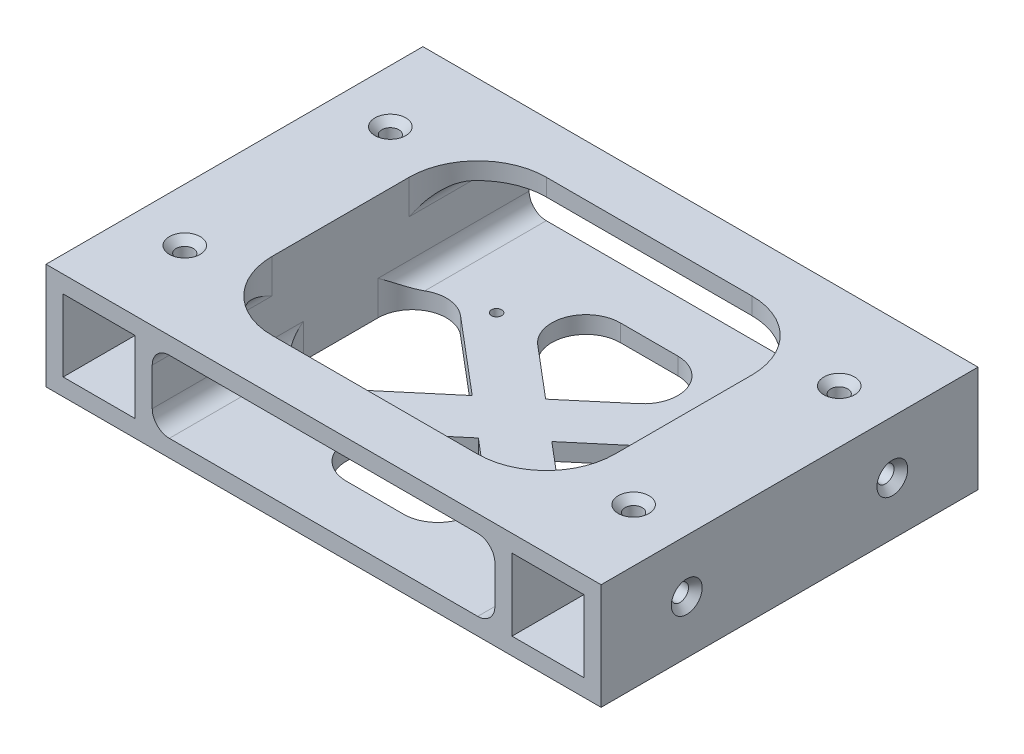
SolidWorks part; units mm, degrees
ref_plane "Top Plane" through (0, 0, 0) normal (0, 0, 1) x (1, 0, 0)
ref_plane "Right Plane" through (0, 0, 0) normal (0, 1, 0) x (1, 0, 0)
ref_plane "Front Plane" through (0, 0, 0) normal (1, 0, 0) x (0, 0, -1)
sketch "Sketch1" plane through (0, 0, 0) normal (0, 0, 1) x (1, 0, 0)
  line L0 (-81, -10.5) -> (-76, -10.5) construction
  line L1 (-55, -10.5) -> (55, -10.5) construction
  line L3 (-55, 10.5) -> (55, 10.5) construction
  line L5 (-55, -10.5) -> (55, 10.5) construction
  line L6 (-55, 10.5) -> (55, -10.5) construction
  line L7 (-81, -15.5) -> (81, -15.5)
  line L8 (-81, -15.5) -> (-81, 15.5)
  line L9 (-81, 15.5) -> (81, 15.5)
  line L10 (81, -15.5) -> (81, 15.5)
  line L11 (-81, -15.5) -> (81, 15.5) construction
  line L12 (-81, 15.5) -> (81, -15.5) construction
  line L13 (55, 10.5) -> (76, 10.5)
  line L14 (55, 10.5) -> (55, -10.5)
  line L15 (55, -10.5) -> (76, -10.5)
  line L16 (76, 10.5) -> (76, -10.5)
  line L17 (-55, 10.5) -> (-76, 10.5)
  line L18 (-55, 10.5) -> (-55, -10.5)
  line L19 (-55, -10.5) -> (-76, -10.5)
  line L20 (-76, 10.5) -> (-76, -10.5)
  line L21 (-76, -15.5) -> (-76, -10.5) construction
  line L22 (-55, 0) -> (-50, 0) construction
  line L23 (50, -10.5) -> (-50, -10.5)
  line L24 (50, -10.5) -> (50, 10.5)
  line L25 (50, 10.5) -> (-50, 10.5)
  line L26 (-50, -10.5) -> (-50, 10.5)
  line L27 (50, -10.5) -> (-50, 10.5) construction
  line L28 (50, 10.5) -> (-50, -10.5) construction
  line L29 (-76, 10.5) -> (-55, -10.5) construction
  line L30 (55, -10.5) -> (76, 10.5) construction
  point P0 (0, 0)
  point P6 (0, 0)
  point P17 (0, 0)
  point P25 (-65.5, 0)
  point P26 (65.5, 0)
  dimension "D1" = 21
  dimension "D2" = 5
  dimension "D3" = 131
extrude "Boss-Extrude1" add sketch "Sketch1" along normal mid plane 110
sketch "Sketch2" plane through (0, -15.5, 0) normal (0, -1, 0) x (1, 0, 0)
  line L0 (-50, -32.4232) -> (-50, 32.4232)
  line L1 (-50, 32.4232) -> (-11.6216, 0)
  line L2 (-11.6216, 0) -> (-50, -32.4232)
  line L3 (-35.7254, 40) -> (0, 9.8182)
  line L4 (0, 9.8182) -> (35.7254, 40)
  line L5 (35.7254, 40) -> (-35.7254, 40)
  line L6 (50, 32.4232) -> (11.6216, 0)
  line L7 (11.6216, 0) -> (50, -32.4232)
  line L8 (50, -32.4232) -> (50, 32.4232)
  line L9 (-35.7254, -40) -> (0, -9.8182)
  line L10 (0, -9.8182) -> (35.7254, -40)
  line L11 (35.7254, -40) -> (-35.7254, -40)
  line L12 (-50, 55) -> (-50, -55) construction
  line L13 (50, 55) -> (50, -55) construction
  line L15 (0, 40) -> (0, 55) construction
  line L16 (0, -40) -> (0, -55) construction
  line L18 (-11.6216, 0) -> (11.6216, 0) construction
  line L19 (0, -9.8182) -> (0, 9.8182) construction
  line L20 (50, 0) -> (81, 0) construction
  line L21 (81, 55) -> (81, -55) construction
  line L22 (-29, 24.5) -> (29, -24.5) construction
  line L23 (-29, -24.5) -> (29, -24.5) construction
  line L24 (-29, -24.5) -> (29, 24.5) construction
  line L25 (29, 24.5) -> (29, -24.5) construction
  line L26 (50, -32.4232) -> (40.3197, -43.8814) construction
  line L27 (81, -55) -> (-81, -55) construction
  line L28 (-81, 55) -> (81, 55) construction
  circle A0 centre (29, -24.5) radius 1.5
  circle A1 centre (-29, -24.5) radius 1.5
  circle A2 centre (29, 24.5) radius 1.5
  circle A3 centre (-29, 24.5) radius 1.5
  point P24 (0, -24.5)
  point P37 (0, 0)
  point P38 (29, 0)
  point P39 (45.1599, -38.1523)
  dimension "D2" = 3
  dimension "D1" = 58
  dimension "D3" = 49
  dimension "D4" = 15
  dimension "D5" = 15
extrude "Cut-Extrude1" cut sketch "Sketch2" against normal up to surface (5 mm away) up to face at (0, -10.5, 0)
sketch "Sketch3" plane through (0, 15.5, 0) normal (0, 1, 0) x (1, 0, 0)
  line L0 (-50, -32.4232) -> (-50, 32.4232) construction
  line L1 (50, 40) -> (-50, 40)
  line L2 (50, 40) -> (50, -40)
  line L3 (50, -40) -> (-50, -40)
  line L4 (-50, 40) -> (-50, -40)
  line L5 (50, 32.4232) -> (50, -32.4232) construction
  line L7 (35.7254, -40) -> (-35.7254, -40) construction
  line L8 (-35.7254, 40) -> (35.7254, 40) construction
extrude "Cut-Extrude2" cut sketch "Sketch3" against normal up to surface (5 mm away) up to face at (0, 10.5, 0)
fillet "Fillet1" radius 10 8 edges at (-35.7254, -13, -40) (35.7254, -13, -40) (35.7254, -13, 40) (-35.7254, -13, 40) (50, -13, 32.4232) (50, -13, -32.4232) (-50, -13, -32.4232) (-50, -13, 32.4232)
fillet "Fillet3" radius 5 8 edges at (-50, 10.5, -47.5) (-50, -10.5, -32.942) (-50, 10.5, 47.5) (-50, -10.5, 32.942) (50, 10.5, -47.5) (50, -10.5, -32.942) (50, 10.5, 47.5) (50, -10.5, 32.942)
sketch "Sketch4" plane through (0, 15.5, 0) normal (0, 1, 0) x (1, 0, 0)
  line L1 (-65.5, 30) -> (65.5, 30) construction
  line L2 (-65.5, 30) -> (-65.5, -30) construction
  line L3 (-65.5, -30) -> (65.5, -30) construction
  line L4 (65.5, 30) -> (65.5, -30) construction
  line L5 (-65.5, 30) -> (65.5, -30) construction
  line L6 (-65.5, -30) -> (65.5, 30) construction
  line L7 (-55, -55) -> (-76, -55) construction
  circle A0 centre (65.5, 30) radius 2.5
  circle A1 centre (65.5, -30) radius 2.5
  circle A2 centre (-65.5, 30) radius 2.5
  circle A3 centre (-65.5, -30) radius 2.5
  point P6 (-65.5, -55)
  point P8 (0, 0)
  dimension "D1" = 5
  dimension "D2" = 60
extrude "Cut-Extrude3" cut sketch "Sketch4" against normal through all
sketch "Sketch5" plane through (-81, 0, 0) normal (-1, 0, 0) x (0, 0, 1)
  line L0 (-30, 0) -> (30, 0) construction
  circle A0 centre (30, 0) radius 2.5
  circle A1 centre (-30, 0) radius 2.5
  point P4 (0, 0)
  point P7 (0, 0)
  dimension "D2" = 5
  dimension "D1" = 60
extrude "Cut-Extrude4" cut sketch "Sketch5" against normal blind 10
mirror "Mirror1" about plane through (0, 0, 0) normal (1, 0, 0) of "Cut-Extrude4"
chamfer "Chamfer1" distance 2 angle 45 12 edges at (-65.5, 15.5, 32.5) (-65.5, 15.5, -27.5) (65.5, 15.5, -27.5) (65.5, 15.5, 32.5) (-65.5, -15.5, 32.5) (-65.5, -15.5, -27.5) (65.5, -15.5, -27.5) (65.5, -15.5, 32.5) (81, 0, -27.5) (81, 0, 32.5) (-81, 0, -27.5) (-81, 0, 32.5)
fillet "Fillet4" radius 20 4 edges at (50, 10.5, 40) (50, 10.5, -40) (-50, 10.5, -40) (-50, 10.5, 40)
ref_plane "Plane1" through (65.5, 0, 0) normal (-1, 0, 0) x (0, 0, 1)
ref_plane "Plane2" through (0, 0, 0) normal (0, 1, 0) x (1, 0, 0)
ref_axis "Axis1" through (65.5, 0, 60.5) along (0, 0, -1)
ref_plane "Plane3" through (0, 0, 0) normal (0, 1, 0) x (1, 0, 0)
ref_plane "Plane4" through (-65.5, 0, 0) normal (1, 0, 0) x (0, 0, -1)
ref_axis "Axis2" through (-65.5, 0, 60.5) along (0, 0, -1)
